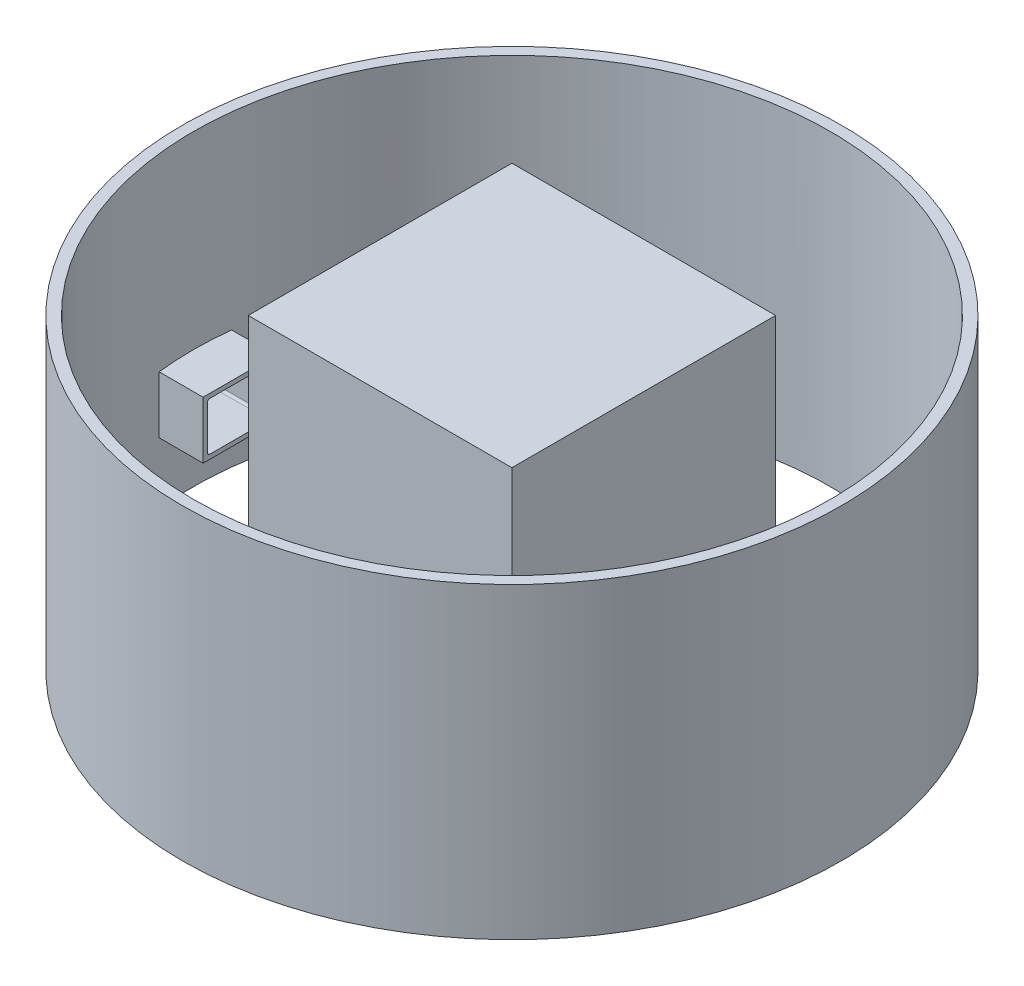
SolidWorks part; units mm, degrees
ref_plane "Alzado" through (0, 0, 0) normal (0, 0, 1) x (1, 0, 0)
ref_plane "Planta" through (0, 0, 0) normal (0, 1, 0) x (1, 0, 0)
ref_plane "Vista lateral" through (0, 0, 0) normal (1, 0, 0) x (0, 0, -1)
sketch "Croquis1" plane through (0, 0, 0) normal (0, 1, 0) x (1, 0, 0)
  circle A0 centre (0, 0) radius 75
  circle A1 centre (0, 0) radius 72.5
  dimension "D1" = 2.5
  dimension "D2" = 145
extrude "Saliente-Extruir1" add sketch "Croquis1" along normal blind 70
sketch "Croquis2" plane through (0, 0, 0) normal (0, -1, 0) x (-1, 0, 0)
  line L0 (36.25, 0) -> (36.25, 65.6577)
  line L3 (-36.25, 0) -> (-36.25, -62.7868)
  line L4 (-36.25, 0) -> (-36.25, 62.7868)
  line L5 (36.25, 0) -> (36.25, -62.7868)
  line L6 (0, 0) -> (0, 4.8983)
  line L7 (0, 0) -> (0, -72.5)
  line L9 (0, 36.25) -> (62.7868, 36.25)
  line L10 (0, 36.25) -> (-62.7868, 36.25)
  line L11 (0, -36.25) -> (-62.7868, -36.25)
  line L12 (0, -36.25) -> (62.7868, -36.25)
  circle A0 centre (0, 0) radius 72.5 construction
  circle A1 centre (0, 0) radius 58.5
  circle A2 centre (0, 0) radius 75 construction
  circle M3 centre (0, 0) radius 72.5
  dimension "D1" = 117
extrude "Saliente-Extruir2" add sketch "Croquis2" against normal blind 10 contours A1 L9 L0 M3 | A1 L5 L12 M3 | A1 L11 L3 M3 | A1 L4 L10 M3 region at (-46.7303, 0, -46.7303) region at (-46.7303, 0, 46.7303) region at (46.7303, 0, -46.7303) region at (46.7303, 0, 46.7303)
sketch "Croquis3" plane through (0, 70, 0) normal (0, 1, 0) x (1, 0, 0)
  line L0 (0, 72.5) -> (0, -72.5)
  line L1 (72.5, 0) -> (-72.5, 0)
  line L3 (-30, -30) -> (30, -30)
  line L4 (-30, -30) -> (-30, 30)
  line L5 (-30, 30) -> (30, 30)
  line L6 (30, -30) -> (30, 30)
  line L7 (-30, -30) -> (30, 30) construction
  line L8 (-30, 30) -> (30, -30) construction
  circle A0 centre (0, 0) radius 72.5 construction
  circle A1 centre (0, 0) radius 72.5
  dimension "D1" = 60
  dimension "D2" = 60
sketch "Croquis4" plane through (0, 0, 0) normal (0, -1, 0) x (-1, 0, 0)
  line L0 (-72.5, 0) -> (72.5, 0)
  line L1 (0, 0) -> (0, -72.5)
  line L2 (0, 0) -> (0, 72.5)
  arc A0 (-62.7868, 36.25) -> (-62.7868, -36.25) centre (0, 0) ccw construction
  arc A1 (62.7868, -36.25) -> (62.7868, 36.25) centre (0, 0) ccw construction
  arc A2 (-36.25, -62.7868) -> (36.25, -62.7868) centre (0, 0) ccw construction
  arc A3 (36.25, 62.7868) -> (-36.25, 62.7868) centre (0, 0) ccw construction
  circle A4 centre (0, 0) radius 78
  circle A5 centre (0, 0) radius 128
  dimension "D1" = 50
extrude "Saliente-Extruir3" add sketch "Croquis3" against normal blind 70 separate body contours L5 L4 L1 L0 | L4 L3 L0 L1 | L3 L6 L1 L0 | L1 L6 L5 L0 region at (15, 70, -15) region at (-15, 70, -15) region at (15, 70, 15) region at (-15, 70, 15)
sketch "Croquis5" plane through (-30, 0, 0) normal (-1, 0, 0) x (0, 0, 1)
  line L0 (0, 0) -> (0, 20.5)
  line L1 (30, 0) -> (-30, 0) construction
  line L2 (-8.25, 27) -> (8.25, 27)
  line L3 (-7.25, 26) -> (7.25, 26)
  line L4 (-7.25, 26) -> (-7.25, 15)
  line L5 (-7.25, 15) -> (7.25, 15)
  line L6 (7.25, 26) -> (7.25, 15)
  line L7 (-7.25, 26) -> (7.25, 15) construction
  line L8 (-7.25, 15) -> (7.25, 26) construction
  line L9 (8.25, 27) -> (8.25, 14)
  line L10 (-8.25, 14) -> (8.25, 14)
  line L11 (-8.25, 27) -> (-8.25, 14)
  dimension "D1" = 20.5
  dimension "D2" = 11
  dimension "D3" = 14.5
  dimension "D4" = 1
extrude "Saliente-Extruir4" add sketch "Croquis5" along normal blind 65 contours L2 L11 L10 L5 L4 L3 L6 L9 region at (-30, 14.2101, -4.125)
sketch "Croquis6" plane through (-95, 0, 0) normal (-1, 0, 0) x (0, 0, 1)
  line L1 (-7.25, 15) -> (7.25, 15)
  line L2 (-7.25, 15) -> (-7.25, 26)
  line L3 (-7.25, 26) -> (7.25, 26)
  line L4 (7.25, 15) -> (7.25, 26)
extrude "Cortar-Extruir2" cut sketch "Croquis6" against normal blind 40
extrude "Cortar-Extruir3" cut sketch "Croquis4" against normal through all contours A5 A4 region at (124.3796, 0, 0)
fillet "Redondeo1" radius 0.5 20 edges at (-74.5449, 20.5, -8.25) (-75, 27, 0) (-75, 14, 0) (-53.8312, 15, 7.25) (-53.8312, 26, 7.25) (-53.8312, 26, -7.25) (-53.8312, 15, -7.25) (-74.5449, 20.5, 8.25) (-76.0537, 27, 8.25) (-77.6623, 20.5, 7.25) (-77.5625, 20.5, 8.25) (-76.0537, 14, 8.25) (-76.0537, 14, -8.25) (-78, 14, 0) (-78, 15, 0) (-78, 26, 0) (-77.6623, 20.5, -7.25) (-77.5625, 20.5, -8.25) (-78, 27, 0) (-76.0537, 27, -8.25)
sketch "Croquis8" plane through (0, 27, 0) normal (0, 1, 0) x (1, 0, 0)
  line L0 (-72.0291, 8.25) -> (-62.0291, 8.25)
  line L1 (-72.0291, 8.25) -> (-30, 8.25) construction
  line L3 (-62.0291, 8.25) -> (-30, 8.25)
  line L4 (-62.0291, 8.25) -> (-62.0291, -8.25)
  line L5 (-62.0291, -8.25) -> (-30, -8.25)
  line L6 (-30, 8.25) -> (-30, -8.25)
  line M2 (-30, 8.25) -> (-72.0291, 8.25)
  line M4 (-72.0291, -8.25) -> (-30, -8.25)
  line M5 (-30, -8.25) -> (-30, 8.25)
  dimension "D1" = 10
extrude "Cortar-Extruir5" cut sketch "Croquis8" against normal through all contours L4 M2 M4 M5 region at (-46.0145, 27, 0)
